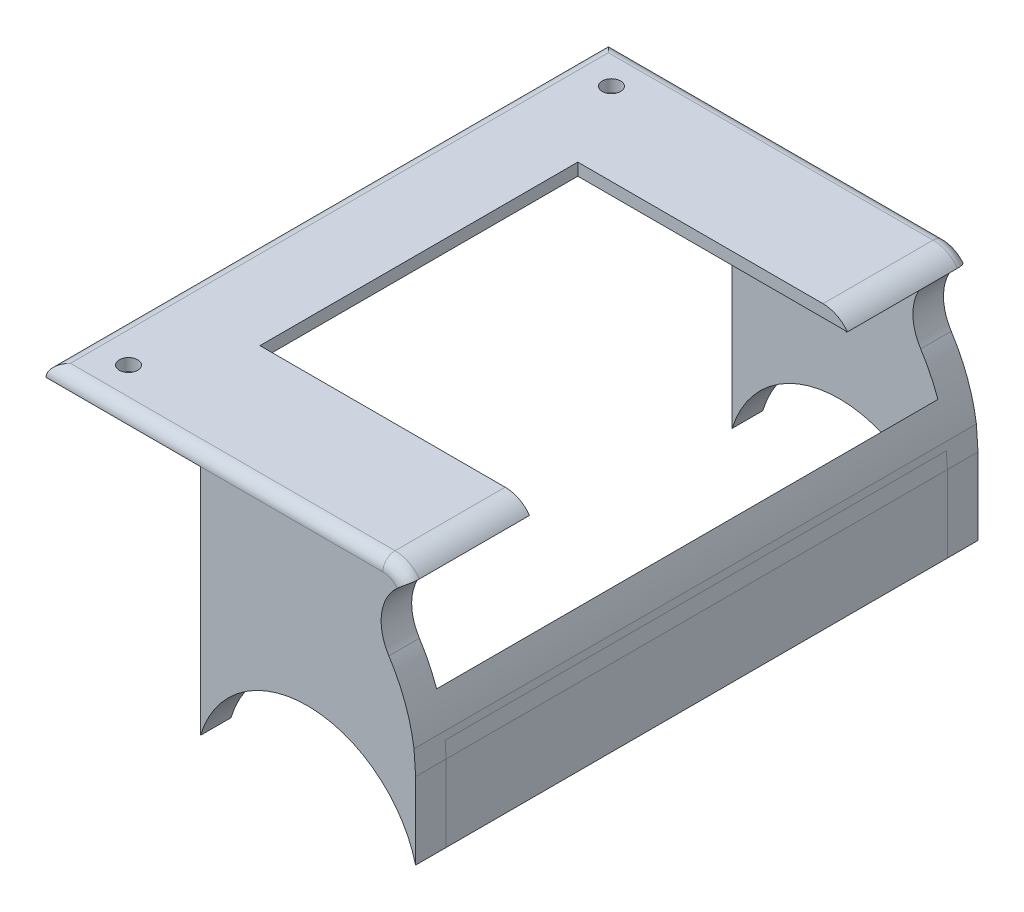
SolidWorks part; units mm, degrees
ref_plane "Спереди" through (0, 0, 0) normal (0, 0, 1) x (1, 0, 0)
ref_plane "Сверху" through (0, 0, 0) normal (0, 1, 0) x (1, 0, 0)
ref_plane "Справа" through (0, 0, 0) normal (1, 0, 0) x (0, 0, -1)
sketch "Эскиз1" plane through (0, 0, 0) normal (0, 1, 0) x (1, 0, 0)
  line L0 (12.6257, -40) -> (-1.1536, -40)
  line L1 (-9.6257, -37.4384) -> (-9.6257, 37.4384)
  line L2 (-1.1536, 40) -> (12.6257, 40)
  line L3 (12.6257, 40) -> (12.6257, 46)
  line L4 (12.6257, 46) -> (-12.6257, 46)
  line L5 (-12.6257, 46) -> (-12.6257, -46)
  line L6 (-12.6257, -46) -> (12.6257, -46)
  line L7 (12.6257, -46) -> (12.6257, -40)
  circle A0 centre (-5.6257, -39.5) radius 1.5
  arc A1 (-1.1536, -40) -> (-9.6257, -37.4384) centre (-5.6257, -39.5) ccw
  arc A2 (-9.6257, 37.4384) -> (-1.1536, 40) centre (-5.6257, 39.5) ccw
  circle A3 centre (-5.6257, 39.5) radius 1.5
extrude "Бобышка-Вытянуть1" add sketch "Эскиз1" along normal blind 2
sketch "Эскиз2" plane through (0, 2, 0) normal (0, 1, 0) x (1, 0, 0)
  line L1 (12.6257, -40) -> (-1.1536, -40) construction
  line L2 (-1.1536, 40) -> (12.6257, 40) construction
  line L4 (1.3743, -40) -> (-1.1536, -40)
  line L5 (-9.6257, -37.4384) -> (-9.6257, 37.4384)
  line L6 (1.3743, 40) -> (-1.1536, 40)
  line L7 (-12.6257, 0) -> (35.1486, 0) construction
  line L8 (-12.6257, 46) -> (-12.6257, -46) construction
  line L9 (41.3743, 26) -> (46.483, 26)
  line L14 (1.3743, -30) -> (41.3743, 30) construction
  line L15 (1.3743, 30) -> (41.3743, -30) construction
  line L16 (12.6257, -46) -> (41.3743, -46)
  line L17 (12.6257, -46) -> (12.6257, -40)
  line L20 (1.3743, -40) -> (12.6257, -40)
  line L24 (12.6257, 46) -> (41.3743, 46)
  line L25 (12.6257, 46) -> (12.6257, 40)
  line L28 (12.6257, 40) -> (1.3743, 40)
  line L33 (41.3743, -26) -> (2.3743, -26)
  line L37 (41.3743, 26) -> (2.3743, 26)
  line L42 (2.3743, -26) -> (2.3743, 26)
  line L43 (41.3743, -46) -> (46.483, -46)
  line L45 (41.3743, -26) -> (46.483, -26)
  line L46 (46.483, -46) -> (46.483, -26)
  line L47 (46.483, 46) -> (46.483, 26)
  line L48 (41.3743, 46) -> (46.483, 46)
  arc A0 (-1.1536, -40) -> (-9.6257, -37.4384) centre (-5.6257, -39.5) ccw
  arc A1 (-9.6257, 37.4384) -> (-1.1536, 40) centre (-5.6257, 39.5) ccw
  point P24 (21.3743, 0)
  dimension "D2" = 60
  dimension "D3" = 40
extrude "Бобышка-Вытянуть2" add sketch "Эскиз2" against normal blind 2
sketch "Эскиз3" plane through (0, 0, 46) normal (0, 0, 1) x (1, 0, 0)
  line L0 (12.6257, -34) -> (46.483, 0) construction
  line L1 (12.6257, -26.3211) -> (49.0077, -26.3211) construction
  line L2 (12.6257, -52.6422) -> (12.6257, 0) construction
  line L3 (47.5757, -22.5094) -> (47.8405, -26.3211)
  line L4 (12.411, -26.3211) -> (12.6257, 0)
  line L5 (-12.6257, 0) -> (46.483, 0) construction
  line L6 (46.483, 0) -> (2.3743, 0) construction
  line L7 (12.6257, 0) -> (28.4699, 0)
  arc A0 (47.8405, -26.3211) -> (28.4699, 0) centre (20.2724, -26.3211) ccw
  arc A2 (47.8405, -26.3211) -> (12.411, -26.3211) centre (30.1257, -43.4146) ccw
  line M4 (-12.6257, 0) -> (46.483, 0)
extrude "Бобышка-Вытянуть3" add sketch "Эскиз3" against normal blind 5 contours A2 L3 A0 L4 M4 region at (27.4102, -11.7118, 46)
sketch "Эскиз4" plane through (0, 0, -46) normal (0, 0, -1) x (-1, 0, 0)
  line L3 (-12.411, -26.3211) -> (-12.6257, 0)
  line L4 (-12.6257, 0) -> (-28.4699, 0)
  line L5 (-47.5757, -22.5094) -> (-47.8405, -26.3211)
  line L6 (-12.411, -26.3211) -> (-12.6257, 0)
  line L7 (-12.6257, 0) -> (-28.4699, 0)
  line L11 (-47.5757, -22.5094) -> (-47.8405, -26.3211)
  arc A2 (-12.411, -26.3211) -> (-47.8405, -26.3211) centre (-30.1257, -43.4146) ccw
  arc A3 (-28.4699, 0) -> (-47.5757, -22.5094) centre (-20.2724, -26.3211) ccw
  arc A4 (-12.411, -26.3211) -> (-47.8405, -26.3211) centre (-30.1257, -43.4146) ccw
  arc A5 (-28.4699, 0) -> (-47.5757, -22.5094) centre (-20.2724, -26.3211) ccw
  dimension "D1" = 0
extrude "Бобышка-Вытянуть4" add sketch "Эскиз4" against normal blind 5
sketch "Эскиз5" plane through (0, 0, 46) normal (0, 0, 1) x (1, 0, 0)
  line L0 (37.4555, 0) -> (20.2724, 0)
  arc A0 (51.48, -30.0814) -> (37.4555, 0) centre (20.2724, -26.3211) ccw
  arc A1 (46.2793, -22.2667) -> (20.2724, 0) centre (20.2724, -26.3211) ccw
  arc A2 (51.48, -30.0814) -> (46.2793, -22.2667) centre (30.1257, -38.6549) ccw
  arc A3 (8.0479, -45.1417) -> (11.2245, -51.7795) centre (30.1257, -38.6549) ccw
  line M8 (47.8405, -26.3211) -> (47.5757, -22.5094)
  arc M9 (47.5757, -22.5094) -> (28.4699, 0) centre (20.2724, -26.3211) ccw
  dimension "D1" = 5.1123
extrude "Бобышка-Вытянуть5" add sketch "Эскиз5" against normal up to surface (87 mm away) contours A2 L0 A1 M8 M9 region at (41.0137, -8.7161, 46) up to face at (30.438, -12.9709, -41)
sketch "Эскиз6" plane through (0, 2, 0) normal (0, 1, 0) x (1, 0, 0)
  line L0 (46.483, -26) -> (2.3743, -26) construction
  line L1 (2.3743, 26) -> (44.3743, 26)
  line L2 (2.3743, 26) -> (2.3743, -26)
  line L3 (2.3743, -26) -> (44.3743, -26)
  line L4 (44.3743, 26) -> (44.3743, -26)
  dimension "D1" = 42
extrude "Вырез-Вытянуть1" cut sketch "Эскиз6" against normal blind 31
fillet "Скругление3" radius 8 2 edges at (28.4699, 0, 36) (28.4699, 0, -36)
fillet "Скругление4" radius 5 2 edges at (46.483, 2, -36) (46.483, 2, 36)
fillet "Скругление5" radius 2 5 edges at (44.7191, 1.4721, -46) (44.7191, 1.4721, 46) (14.9286, 2, -46) (-12.6257, 2, 0) (14.9286, 2, 46)
sketch "Эскиз7" plane through (0, 0, -46) normal (0, 0, -1) x (-1, 0, 0)
  line L1 (-12.6257, 0) -> (-13.1257, 0)
  line L2 (-12.6257, 0) -> (-12.6257, -24.4952)
  line L3 (-12.6257, -24.4952) -> (-13.1257, -24.4952)
  line L4 (-13.1257, 0) -> (-13.1257, -24.4952)
  dimension "D1" = 0.5
extrude "Вырез-Вытянуть2" cut sketch "Эскиз7" against normal through all rebuild error yes
sketch "Эскиз8" plane through (0, 0, 0) normal (0, -1, 0) x (1, 0, 0)
  line L0 (-12.6257, 0) -> (47.6623, 0) construction
  line L1 (-12.6257, -46) -> (-12.6257, 46) construction
  line L2 (47.6623, -41) -> (47.6623, 41) construction
  line L4 (13.1257, -41) -> (46.2793, -41)
  line L5 (13.1257, -41) -> (13.1257, 41)
  line L6 (13.1257, 41) -> (46.2793, 41)
  line L7 (46.2793, -41) -> (46.2793, 41)
extrude "Вырез-Вытянуть3" cut sketch "Эскиз8" along normal blind 31 contours L7 L6 L5 L4
sketch "Эскиз9" plane through (0, 2, 0) normal (0, 1, 0) x (1, 0, 0)
  line L1 (2.3743, -26) -> (46.483, -26)
  line L2 (2.3743, -26) -> (2.3743, 26)
  line L3 (2.3743, 26) -> (46.483, 26)
  line L4 (46.483, -26) -> (46.483, 26)
sketch "Эскиз10" plane through (0, 0, 46) normal (0, 0, 1) x (1, 0, 0)
  line L0 (12.6257, -26.1013) -> (12.6257, -38.1038)
  line L1 (42.483, 0) -> (12.6257, 0) construction
  line L2 (47.8405, -26.3211) -> (47.8405, -38.8713)
  line L6 (42.483, 0) -> (12.6257, 0)
  line L7 (12.6257, 0) -> (12.411, -26.3211)
  line L8 (47.8405, -26.3211) -> (47.5757, -22.5094)
  line L10 (12.6257, 0) -> (12.411, -26.3211)
  arc A0 (47.8405, -38.8713) -> (12.6257, -38.1038) centre (30.1257, -43.4146) ccw
  arc A1 (47.8405, -26.3211) -> (12.411, -26.3211) centre (30.1257, -43.4146) ccw
  arc A5 (44.8391, -1.1429) -> (43.4625, -11.4141) centre (50.192, -7.0882) ccw
  arc A6 (44.8391, -1.1429) -> (42.483, 0) centre (42.483, -3) ccw
  arc A7 (47.8405, -26.3211) -> (12.411, -26.3211) centre (30.1257, -43.4146) ccw
  arc A8 (47.5757, -22.5094) -> (43.4625, -11.4141) centre (20.2724, -26.3211) ccw
  arc A11 (47.8405, -26.3211) -> (12.411, -26.3211) centre (30.1257, -43.4146) ccw
  arc M14 (12.411, -26.3211) -> (47.8405, -26.3211) centre (30.1257, -43.4146) cw
  dimension "D1" = 90
  dimension "D2" = 0
extrude "Бобышка-Вытянуть6" add sketch "Эскиз10" against normal up to surface (5 mm away) contours A0 L2 L0 M14 region at (30.2768, -19.2033, 46) up to face at (38.5403, -13.2373, 41)
sketch "Эскиз11" plane through (0, 0, 0) normal (0, -1, 0) x (1, 0, 0)
  line L0 (-12.6257, 0) -> (47.6623, 0) construction
  line L1 (12.411, 41) -> (12.6257, 41)
  line L2 (12.411, 41) -> (12.411, 46)
  line L3 (12.411, 46) -> (12.6257, 46)
  line L4 (12.6257, 41) -> (12.6257, 46)
  line L5 (-12.6257, -46) -> (-12.6257, 46) construction
  line L6 (47.6623, -41) -> (47.6623, 41) construction
  line L7 (12.411, -46) -> (12.6257, -46)
  line L8 (12.6257, -41) -> (12.6257, -46)
  line L9 (12.411, -41) -> (12.411, -46)
  line L10 (12.411, -41) -> (12.6257, -41)
extrude "Вырез-Вытянуть4" cut sketch "Эскиз11" along normal through all
sketch "Эскиз12" plane through (0, 0, -46) normal (0, 0, -1) x (-1, 0, 0)
  line L0 (-12.6257, -26.1013) -> (-12.6257, -38.1038)
  line L1 (-47.8405, -26.3211) -> (-47.8405, -38.8713)
  arc A0 (-12.6257, -26.1013) -> (-47.8405, -26.3211) centre (-30.1257, -43.4146) ccw
  arc A1 (-12.6257, -38.1038) -> (-47.8405, -38.8713) centre (-30.1257, -43.4146) ccw
extrude "Бобышка-Вытянуть7" add sketch "Эскиз12" against normal up to surface (5 mm away) up to face at (38.5693, -13.2251, -41)
sketch "Эскиз13" plane through (0, 0, 41) normal (0, 0, -1) x (-1, 0, 0)
  line L0 (-47.6623, -23.7558) -> (-47.8405, -26.3211)
  line L1 (-47.8405, -26.3211) -> (-47.8405, -38.8713)
  line L2 (-46.2793, -22.2667) -> (-46.3405, -23.1466)
  line L3 (-46.3405, -23.1466) -> (-46.3405, -34.9567)
  line L4 (-47.6623, -23.7558) -> (-46.2793, -22.2667)
  line L10 (-12.6257, -38.1038) -> (-12.6257, 0)
  line L11 (-12.6257, 0) -> (-46.2793, 0)
  line L12 (-46.2793, 0) -> (-46.2793, -0.1103)
  line L13 (-46.2793, -17.1757) -> (-46.2793, -22.2667)
  line L14 (-47.6623, -23.7558) -> (-47.8405, -26.3211)
  line L15 (-47.8405, -26.3211) -> (-47.8405, -38.8713)
  line L16 (-12.6257, -38.1038) -> (-12.6257, 0)
  line L17 (-12.6257, 0) -> (-46.2793, 0)
  line L18 (-46.2793, 0) -> (-46.2793, -0.1103)
  line L20 (-47.6623, -23.7558) -> (-47.8405, -26.3211)
  line L21 (-47.8405, -26.3211) -> (-47.8405, -38.8713)
  arc A0 (-46.3405, -34.9567) -> (-47.8405, -38.8713) centre (-30.1257, -43.4146) ccw
  arc A5 (-43.4625, -11.4141) -> (-46.2793, -0.1103) centre (-50.192, -7.0882) ccw
  arc A6 (-43.4625, -11.4141) -> (-46.2793, -17.1757) centre (-20.2724, -26.3211) ccw
  arc A7 (-46.2793, -22.2667) -> (-47.6623, -23.7558) centre (-30.1257, -38.6549) ccw
  arc A8 (-12.6257, -38.1038) -> (-47.8405, -38.8713) centre (-30.1257, -43.4146) ccw
  arc A9 (-43.4625, -11.4141) -> (-46.2793, -0.1103) centre (-50.192, -7.0882) ccw
  arc A10 (-43.4625, -11.4141) -> (-46.2793, -17.1757) centre (-20.2724, -26.3211) ccw
  arc A12 (-12.6257, -38.1038) -> (-47.8405, -38.8713) centre (-30.1257, -43.4146) ccw
  line M23 (-47.6623, -23.7558) -> (-47.8405, -26.3211)
  line M24 (-47.8405, -26.3211) -> (-47.8405, -38.8713)
  arc M25 (-47.8405, -38.8713) -> (-12.6257, -38.1038) centre (-30.1257, -43.4146) cw
  dimension "D1" = 0
  dimension "D2" = 1.5
  dimension "D3" = 0
extrude "Бобышка-Вытянуть9" add sketch "Эскиз13" along normal up to surface (82 mm away) separate body contours L4 L3 L2 M23 M24 M25 region at (47.1029, -29.9986, 41) up to face at (39.5209, -16.3956, -41)
